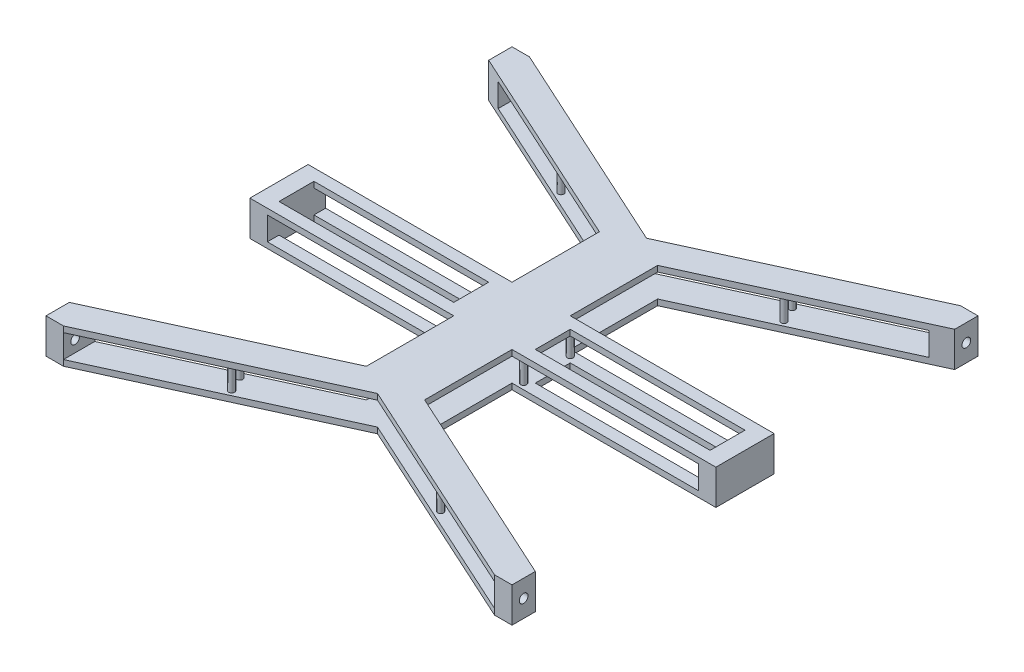
SolidWorks part; units mm, degrees
ref_plane "Front Plane" through (0, 0, 0) normal (0, 0, 1) x (1, 0, 0)
ref_plane "Top Plane" through (0, 0, 0) normal (0, 1, 0) x (1, 0, 0)
ref_plane "Right Plane" through (0, 0, 0) normal (1, 0, 0) x (0, 0, -1)
sketch "Sketch1" plane through (0, 0, 0) normal (0, 1, 0) x (1, 0, 0)
  line L1 (-9.9, 0) -> (9.9, 0) construction
  line L2 (80, 10) -> (80, -10)
  line L3 (80, -10) -> (10, -10)
  line L4 (10, -10) -> (10, -40)
  line L5 (10, -40) -> (80, -72)
  line L6 (80, -72) -> (80, -80)
  line L7 (80, -80) -> (74, -80)
  line L8 (74, -80) -> (0, -46.1714)
  line L9 (0, -9.9) -> (0, 9.9) construction
  line L11 (-80, 10) -> (-80, -10)
  line L12 (-80, -10) -> (-10, -10)
  line L13 (-10, -10) -> (-10, -40)
  line L14 (-10, -40) -> (-80, -72)
  line L15 (-80, -72) -> (-80, -80)
  line L16 (-80, -80) -> (-74, -80)
  line L17 (-74, -80) -> (0, -46.1714)
  line L18 (80, 10) -> (10, 10)
  line L19 (10, 10) -> (10, 40)
  line L20 (80, 80) -> (74, 80)
  line L21 (80, 72) -> (80, 80)
  line L22 (10, 40) -> (80, 72)
  line L23 (74, 80) -> (0, 46.1714)
  line L24 (-80, 72) -> (-80, 80)
  line L25 (-80, 80) -> (-74, 80)
  line L26 (-74, 80) -> (0, 46.1714)
  line L27 (-10, 40) -> (-80, 72)
  line L28 (-80, 10) -> (-10, 10)
  line L29 (-10, 10) -> (-10, 40)
  point P21 (80, 0)
  point P33 (-80, 0)
  dimension "D3" = 10
  dimension "D5" = 8
  dimension "D6" = 30
  dimension "D8" = 6
  dimension "D1" = 80
  dimension "D2" = 80
  dimension "D4" = 80
  dimension "D7" = 10
extrude "Boss-Extrude1" add sketch "Sketch1" along normal blind 6 and the other way blind 6
sketch "Sketch2" plane through (0, 0, 80) normal (0, 0, 1) x (1, 0, 0)
  line L0 (-74, -6) -> (-74, 6) construction
  line L1 (-74, -4) -> (74, -4)
  line L2 (-74, -4) -> (-74, 4)
  line L3 (-74, 4) -> (74, 4)
  line L4 (74, -4) -> (74, 4)
  line L5 (74, -6) -> (74, 6) construction
  line L7 (132, 0) -> (-132, 0) construction
  dimension "D1" = 4
  dimension "D2" = 4
extrude "Cut-Extrude1" cut sketch "Sketch2" against normal blind 160
sketch "Sketch4" plane through (0, 6, 0) normal (0, 1, 0) x (1, 0, 0)
  line L0 (-9.9, 0) -> (9.9, 0) construction
  line L1 (-74, 6) -> (-14, 6)
  line L2 (-74, 6) -> (-74, -6)
  line L3 (-74, -6) -> (-14, -6)
  line L4 (-14, 6) -> (-14, -6)
  line L5 (-80, 10) -> (-80, -10) construction
  line L7 (0, -9.9) -> (0, 9.9) construction
  line L8 (74, -6) -> (14, -6)
  line L9 (14, 6) -> (14, -6)
  line L10 (74, 6) -> (14, 6)
  line L11 (74, 6) -> (74, -6)
  dimension "D1" = 6
  dimension "D2" = 6
  dimension "D3" = 6
  dimension "D4" = 60
extrude "Cut-Extrude2" cut sketch "Sketch4" against normal blind 12
sketch "Sketch5" plane through (0, -4, 0) normal (0, 1, 0) x (1, 0, 0)
  line L1 (-10, -40) -> (-74, -69.2571) construction
  line L2 (-74, -80) -> (0, -46.1714) construction
  line L4 (-39.1032, -53.3043) -> (-35.0411, -62.1902) construction
  line L5 (0, -9.9) -> (0, 9.9) construction
  line L6 (-14, 6) -> (-14, -6) construction
  line L7 (-14, -6) -> (-74, -6) construction
  line L8 (-9.9, 0) -> (9.9, 0) construction
  circle A0 centre (-35.8726, -60.3713) radius 1
  circle A1 centre (-38.2717, -55.1233) radius 1
  circle A3 centre (-12, -8) radius 1
  circle A4 centre (0, -40.1714) radius 1
  circle A5 centre (12, -8) radius 1
  circle A6 centre (35.8726, -60.3713) radius 1
  circle A7 centre (38.2717, -55.1233) radius 1
  circle A8 centre (38.2717, 55.1233) radius 1
  circle A9 centre (35.8726, 60.3713) radius 1
  circle A10 centre (-35.8726, 60.3713) radius 1
  circle A11 centre (-38.2717, 55.1233) radius 1
  circle A12 centre (0, 40.1714) radius 1
  circle A13 centre (12, 8) radius 1
  circle A14 centre (-12, 8) radius 1
  dimension "D1" = 2
  dimension "D2" = 2
  dimension "D4" = 2
  dimension "D3" = 2
  dimension "D6" = 2
  dimension "D8" = 32
  dimension "D5" = 2
  dimension "D7" = 90
  dimension "D9" = 6
  dimension "D10" = 2
  dimension "D11" = 2
extrude "Boss-Extrude2" add sketch "Sketch5" along normal blind 8
sketch "Sketch6" plane through (0, 0, 0) normal (1, 0, 0) x (0, 0, -1)
  line L0 (-72, 0) -> (-80, 0) construction
  line L1 (72, 0) -> (80, 0) construction
  circle A0 centre (-76, 0) radius 1.5
  circle A1 centre (76, 0) radius 1.5
  point P6 (-76, 0)
  point P7 (0, 0)
  point P10 (76, 0)
  dimension "D1" = 3
extrude "Cut-Extrude3" cut sketch "Sketch6" against normal through all both and the other way through all
equation "\"A\"= 2"
equation "\"D5@Sketch1\"=4*\"A\""
equation "\"D6@Sketch1\"=15*\"A\""
equation "\"D8@Sketch1\"=3*\"A\""
equation "\"D1@Sketch1\"=40*\"A\""
equation "\"D2@Sketch1\"=40*\"A\""
equation "\"D4@Sketch1\"=40*\"A\""
equation "\"D7@Sketch1\"=5*\"A\""
equation "\"D1@Boss-Extrude1\"=3*\"A\""
equation "\"D2@Boss-Extrude1\"=3*\"A\""
equation "\"D1@Sketch2\"=2*\"A\""
equation "\"D2@Sketch2\"=2*\"A\""
equation "\"D1@Sketch4\"=3*\"A\""
equation "\"D2@Sketch4\"=3*\"A\""
equation "\"D3@Sketch4\"=3*\"A\""
equation "\"D4@Sketch4\"=30*\"A\""
equation "\"D1@Cut-Extrude2\"=6*\"A\""
equation "\"D1@Cut-Extrude1\"=80*\"A\""
equation "\"D3@Sketch1\"=5*\"A\""
equation "\"D1@Sketch5\"=\"A\""
equation "\"D2@Sketch5\"=\"A\""
equation "\"D4@Sketch5\"=\"A\""
equation "\"D6@Sketch5\"=\"A\""
equation "\"D8@Sketch5\"=16*\"A\""
equation "\"D5@Sketch5\"=\"A\""
equation "\"D3@Sketch5\"=\"A\""
equation "\"D9@Sketch5\"=3*\"A\""
equation "\"D10@Sketch5\"=\"A\""
equation "\"D11@Sketch5\"=\"A\""
equation "\"D1@Boss-Extrude2\"=4*\"A\""
